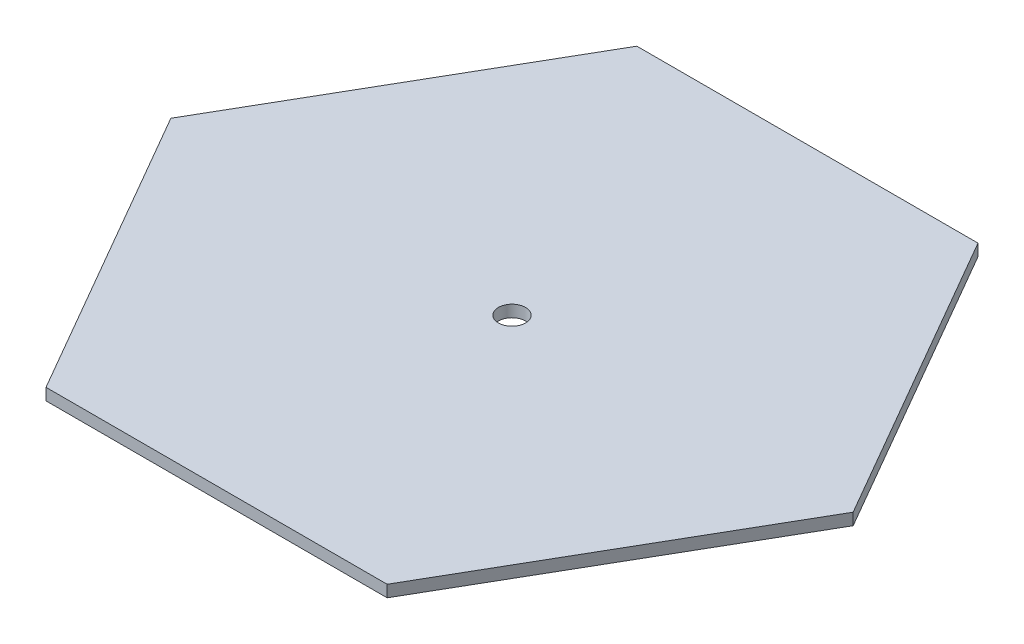
SolidWorks part; units mm, degrees
ref_plane "Front Plane" through (0, 0, 0) normal (0, 0, 1) x (1, 0, 0)
ref_plane "Top Plane" through (0, 0, 0) normal (0, 1, 0) x (1, 0, 0)
ref_plane "Right Plane" through (0, 0, 0) normal (1, 0, 0) x (0, 0, -1)
sketch "Sketch1" plane through (0, 0, 0) normal (0, 1, 0) x (1, 0, 0)
  line L1 (72.5, 125.5737) -> (-72.5, 125.5737)
  line L2 (-72.5, 125.5737) -> (-145, 0)
  line L3 (-145, 0) -> (-72.5, -125.5737)
  line L4 (-72.5, -125.5737) -> (72.5, -125.5737)
  line L5 (72.5, -125.5737) -> (145, 0)
  line L6 (145, 0) -> (72.5, 125.5737)
  circle A0 centre (0, 0) radius 125.5737 construction
  dimension "D1" = 145
extrude "Boss-Extrude1" add sketch "Sketch1" along normal blind 5
sketch "Sketch2" plane through (0, 0, 0) normal (0, 1, 0) x (1, 0, 0)
  line L0 (0, 0) -> (108.75, 62.7868) construction
  line L1 (145, 0) -> (72.5, 125.5737) construction
  line L2 (75.5513, 30.8586) -> (53.0513, -8.1125) construction
  line L3 (66.5368, -29.7548) -> (27.5657, -7.2548) construction
  line L6 (33.5657, 3.1375) -> (72.5368, -19.3625) construction
  line L7 (72.5368, -19.3625) -> (95.0368, 19.6086) construction
  line L8 (95.0368, 19.6086) -> (56.0657, 42.1086) construction
  line L9 (56.0657, 42.1086) -> (33.5657, 3.1375) construction
  line L10 (-14.0657, -30.6375) -> (-53.0368, -53.1375) construction
  line L11 (8.4343, -69.6086) -> (-14.0657, -30.6375) construction
  line L12 (-30.5368, -92.1086) -> (8.4343, -69.6086) construction
  line L13 (-53.0368, -53.1375) -> (-30.5368, -92.1086) construction
  line L14 (-19.5, 27.5) -> (-19.5, 72.5) construction
  line L15 (-64.5, 27.5) -> (-19.5, 27.5) construction
  line L16 (-64.5, 72.5) -> (-64.5, 27.5) construction
  line L17 (-19.5, 72.5) -> (-64.5, 72.5) construction
  line L19 (53.0513, -8.1125) -> (43.3013, -25) construction
  line L21 (108.75, -62.7868) -> (0, 0) construction
  line L22 (72.5, -125.5737) -> (145, 0) construction
  point P9 (47.0513, -18.5048)
  point P18 (33.5657, 3.1375)
  point P19 (56.0657, 42.1086)
  point P20 (95.0368, 19.6086)
  point P21 (72.5368, -19.3625)
  point P31 (0, 0)
  dimension "D1" = 45
  dimension "D2" = 45
  dimension "D4" = 7.5
  dimension "D5" = 12
  dimension "D6" = 50
  dimension "D3" = 3
sketch "Sketch5" plane through (0, 5, 0) normal (0, 1, 0) x (1, 0, 0)
  circle A0 centre (0, 0) radius 5.7532
extrude "Cut-Extrude1" cut sketch "Sketch5" against normal through all
